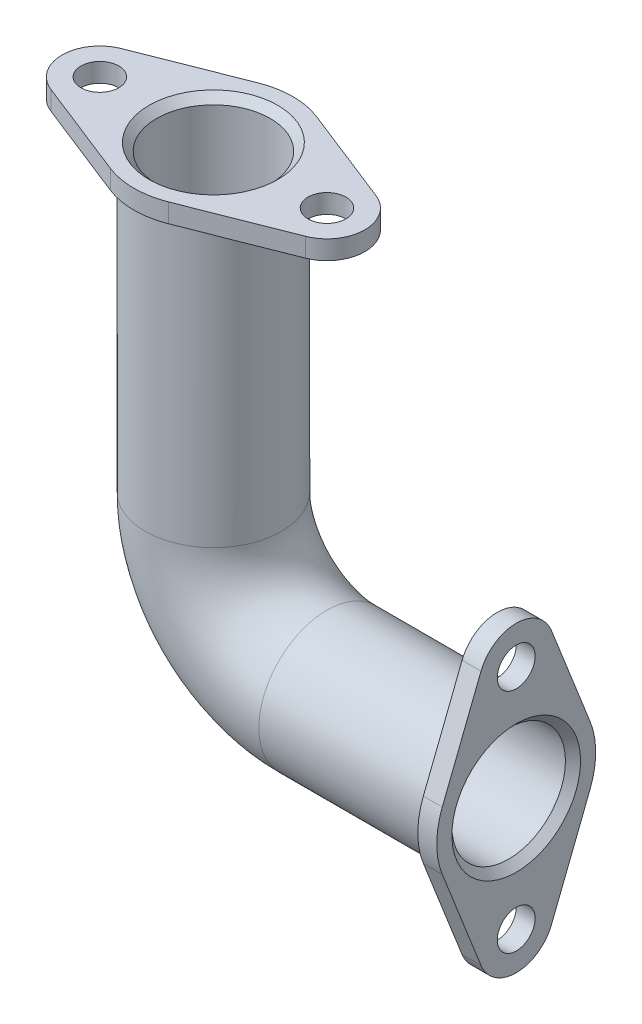
SolidWorks part; units mm, degrees
material "2024-T361"
ref_plane "Front Plane" through (0, 0, 0) normal (0, 0, 1) x (1, 0, 0)
ref_plane "Top Plane" through (0, 0, 0) normal (0, 1, 0) x (1, 0, 0)
ref_plane "Right Plane" through (0, 0, 0) normal (1, 0, 0) x (0, 0, -1)
sketch "Sketch1" plane through (0, 0, 0) normal (0, 0, 1) x (1, 0, 0)
  line L2 (60, 0) -> (150, 0)
  line L3 (0, 60) -> (0, 210)
  arc A0 (0, 60) -> (60, 0) centre (60, 60) ccw
  point P7 (0, 0)
  dimension "D1" = 90
  dimension "D3" = 60
  dimension "D2" = 150
ref_plane "Plane1" through (150, 0, 0) normal (1, 0, 0) x (0, 0, -1)
sketch "Sketch2" plane through (150, 0, 0) normal (1, 0, 0) x (0, 0, -1)
  circle A0 centre (0, 0) radius 36
  dimension "D1" = 72
sweep "Sweep1" add profiles "Sketch2" path "Sketch1"
shell "Shell1" thickness 6 removed face at (150, 0, -36) removed face at (0, 210, -36)
sketch "Sketch4" plane through (0, 210, 0) normal (0, 1, 0) x (1, 0, 0)
  line L0 (0, 0) -> (-30, 0) construction
  line L1 (-67.3333, 18.607) -> (-15.4, 39.0748)
  line L2 (67.3333, 18.607) -> (15.4, 39.0748)
  line L3 (-67.3333, -18.607) -> (-15.4, -39.0748)
  line L4 (15.4, -39.0748) -> (67.3333, -18.607)
  line L5 (-50, 0) -> (-181.1762, 0) construction
  circle A0 centre (0, 0) radius 30
  arc A1 (-15.4, -39.0748) -> (15.4, -39.0748) centre (0, 0) ccw
  circle A2 centre (60, 0) radius 10
  arc A3 (67.3333, -18.607) -> (67.3333, 18.607) centre (60, 0) ccw
  circle A4 centre (-60, 0) radius 10
  arc A5 (-67.3333, 18.607) -> (-67.3333, -18.607) centre (-60, 0) ccw
  arc A6 (15.4, 39.0748) -> (-15.4, 39.0748) centre (0, 0) ccw
  dimension "D1" = 84
  dimension "D2" = 20
  dimension "D3" = 40
  dimension "D4" = 60
  dimension "D5" = 60
extrude "Boss-Extrude1" add sketch "Sketch4" along normal blind 10
sketch "Sketch5" plane through (150, 0, 0) normal (1, 0, 0) x (0, 0, -1)
  line L0 (-18.6071, 67.3333) -> (-39.0748, 15.4)
  line L1 (18.607, 67.3334) -> (39.0748, 15.4)
  line L2 (-18.607, -67.3333) -> (-39.0748, -15.4)
  line L3 (18.607, -67.3333) -> (39.0748, -15.4)
  circle A0 centre (0, 0) radius 30
  circle A1 centre (0, -60) radius 10
  arc A2 (-18.607, -67.3333) -> (18.607, -67.3333) centre (0, -60) ccw
  circle A3 centre (-0.0001, 60) radius 10
  arc A5 (-39.0748, 15.4) -> (-39.0748, -15.4) centre (0, 0) ccw
  arc A6 (18.607, 67.3334) -> (-18.6071, 67.3333) centre (-0.0001, 60) ccw
  arc A7 (39.0748, -15.4) -> (39.0748, 15.4) centre (0, 0) ccw
  dimension "D1" = 84
  dimension "D3" = 20
  dimension "D4" = 60
  dimension "D5" = 60
extrude "Boss-Extrude2" add sketch "Sketch5" along normal blind 10
chamfer "Chamfer2" distance 4 angle 45 2 edges at (160, 0, -30) (-30, 220, 0)
